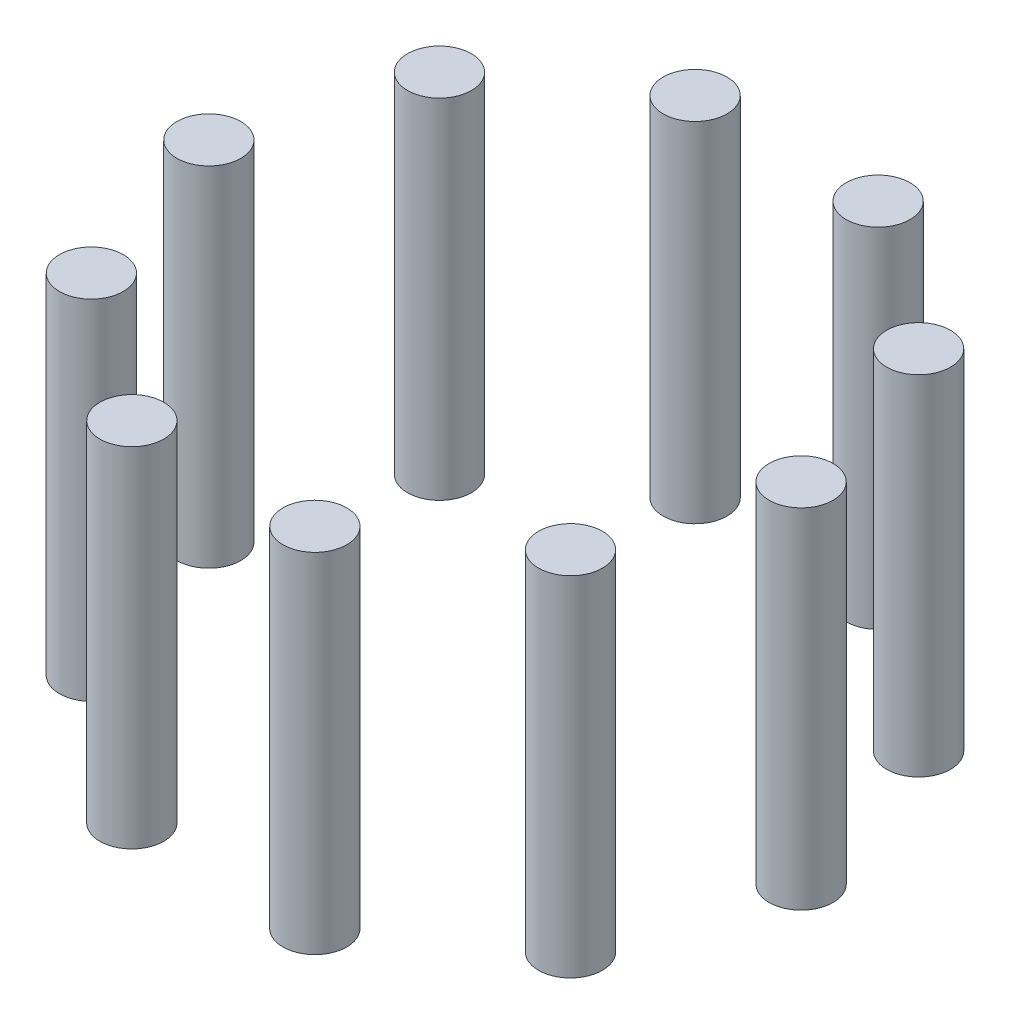
SolidWorks part; units mm, degrees
ref_plane "Front Plane" through (0, 0, 0) normal (0, 0, 1) x (1, 0, 0)
ref_plane "Top Plane" through (0, 0, 0) normal (0, 1, 0) x (1, 0, 0)
ref_plane "Right Plane" through (0, 0, 0) normal (1, 0, 0) x (0, 0, -1)
sketch "Sketch1" plane through (0, 0, 0) normal (0, 1, 0) x (1, 0, 0)
  circle A1 centre (51, 0) radius 5.5
  circle A2 centre (41.2599, -29.977) radius 5.5
  circle A3 centre (15.7599, -48.5039) radius 5.5
  circle A4 centre (-15.7599, -48.5039) radius 5.5
  circle A5 centre (-41.2599, -29.977) radius 5.5
  circle A6 centre (-51, 0) radius 5.5
  circle A7 centre (-41.2599, 29.977) radius 5.5
  circle A8 centre (-15.7599, 48.5039) radius 5.5
  circle A9 centre (15.7599, 48.5039) radius 5.5
  circle A10 centre (41.2599, 29.977) radius 5.5
  point P25 (0, 0)
  dimension "D1" = 10
extrude "Boss-Extrude1" add sketch "Sketch1" along normal blind 60
